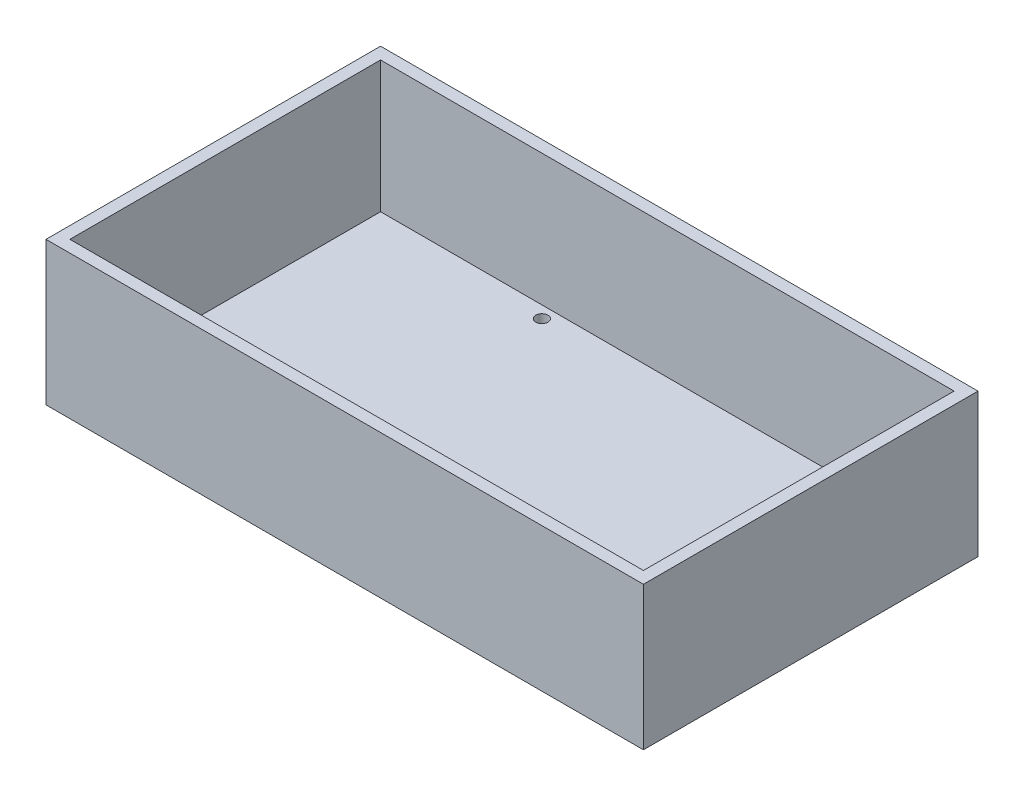
SolidWorks part; units mm, degrees
material "Polypropylene"
ref_plane "正面" through (0, 0, 0) normal (0, 0, 1) x (1, 0, 0)
ref_plane "平面" through (0, 0, 0) normal (0, 1, 0) x (1, 0, 0)
ref_plane "右側面" through (0, 0, 0) normal (1, 0, 0) x (0, 0, -1)
sketch "ｽｹｯﾁ1" plane through (0, 0, 0) normal (0, 1, 0) x (1, 0, 0)
  line L1 (-125, 70) -> (125, 70)
  line L2 (-125, 70) -> (-125, -70)
  line L3 (-125, -70) -> (125, -70)
  line L4 (125, 70) -> (125, -70)
  line L5 (-125, 70) -> (125, -70) construction
  line L6 (-125, -70) -> (125, 70) construction
  point P0 (0, 0)
  dimension "D1" = 250
  dimension "D2" = 140
extrude "ﾎﾞｽ - 押し出し1" add sketch "ｽｹｯﾁ1" along normal blind 60
shell "ｼｪﾙ1" thickness 5 removed face at (0, 60, 0)
sketch "ｽｹｯﾁ2" plane through (0, 5, 0) normal (0, 1, 0) x (1, 0, 0)
  line L0 (115, 70) -> (115, -70) construction
  line L1 (125, 70) -> (-125, 70) construction
  line L2 (-125, -70) -> (125, -70) construction
  line L3 (115, -70) -> (-47.5, -70) construction
  line L4 (-47.5, -70) -> (-47.5, 70) construction
  line L6 (125, -70) -> (125, 70) construction
  line L7 (-47.5, 0) -> (115, 0) construction
  line L8 (33.75, 70) -> (33.75, -70) construction
  circle A0 centre (115, 60) radius 2.55
  circle A1 centre (115, -60) radius 2.55
  circle A2 centre (-47.5, -60) radius 2.55
  circle A3 centre (-47.5, 60) radius 2.55
  point P18 (33.75, 0)
  dimension "D3" = 5.1
  dimension "D1" = 162.5
  dimension "D2" = 10
  dimension "D4" = 60
extrude "ｶｯﾄ - 押し出し1" cut sketch "ｽｹｯﾁ2" against normal through all
